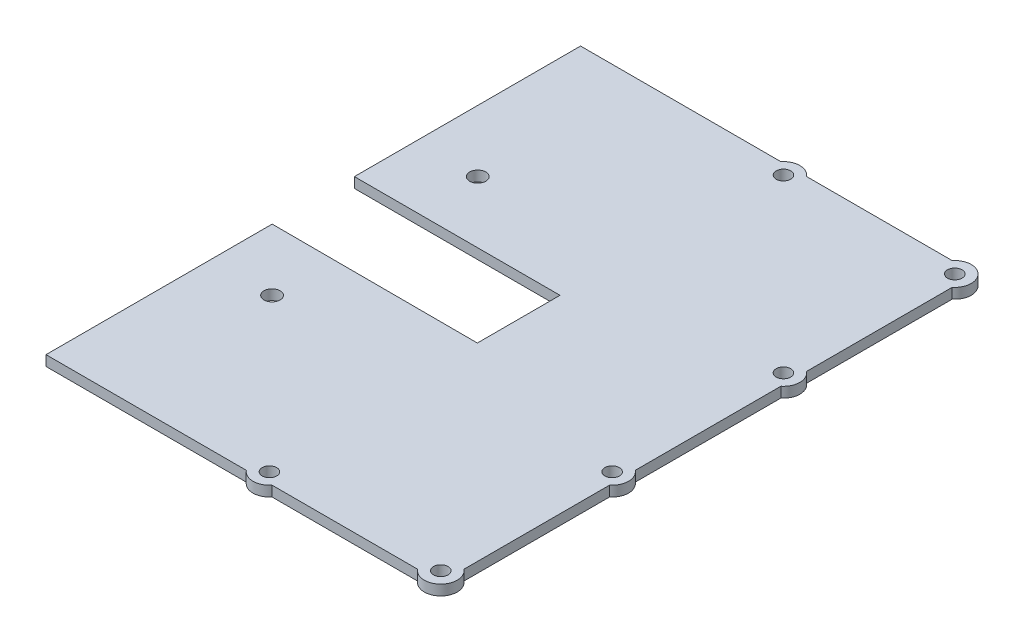
SolidWorks part; units mm, degrees
material "Aluminum"
ref_plane "Front Plane" through (0, 0, 0) normal (0, 0, 1) x (1, 0, 0)
ref_plane "Top Plane" through (0, 0, 0) normal (0, 1, 0) x (1, 0, 0)
ref_plane "Right Plane" through (0, 0, 0) normal (1, 0, 0) x (0, 0, -1)
sketch "Sketch1" plane through (0, 0, 0) normal (0, 1, 0) x (1, 0, 0)
  circle A0 centre (65.8401, 3.175) radius 2.2479
  circle A1 centre (118.7568, 3.175) radius 2.2479
  circle A2 centre (118.7568, 56.0917) radius 2.2479
  circle A3 centre (118.7568, 109.0083) radius 2.2479
  circle A4 centre (118.7568, 161.925) radius 2.2479
  circle A5 centre (65.8401, 161.925) radius 2.2479
  line B0 (0, 165.1) -> (61.8745, 165.1)
  line B1 (0, 95.25) -> (0, 165.1)
  line B2 (0, 69.85) -> (0, 0)
  line B3 (61.8745, 0) -> (0, 0)
  line B4 (114.7912, 0) -> (69.8057, 0)
  line B5 (121.9318, 52.1261) -> (121.9318, 7.1406)
  line B6 (121.9318, 105.0428) -> (121.9318, 60.0572)
  line B7 (121.9318, 157.9594) -> (121.9318, 112.9739)
  line B8 (69.8057, 165.1) -> (114.7912, 165.1)
  line B9 (0, 95.25) -> (63.5, 95.25)
  line B10 (63.5, 95.25) -> (63.5, 69.7245)
  line B11 (63.5, 69.7245) -> (0, 69.85)
  arc B12 (69.8057, 165.1) -> (61.8745, 165.1) centre (65.8401, 161.925) ccw
  arc B13 (61.8745, 0) -> (69.8057, 0) centre (65.8401, 3.175) ccw
  arc B14 (114.7912, 0) -> (121.9318, 7.1406) centre (118.7568, 3.175) ccw
  arc B15 (121.9318, 52.1261) -> (121.9318, 60.0572) centre (118.7568, 56.0917) ccw
  arc B16 (121.9318, 105.0428) -> (121.9318, 112.9739) centre (118.7568, 109.0083) ccw
  arc B17 (121.9318, 157.9594) -> (114.7912, 165.1) centre (118.7568, 161.925) ccw
  dimension "D1" = 4.4958
sketch_block_instance "Block-bottomplate-1"
sketch_block "Block-bottomplate" parameters "D1"=63.5
extrude "Boss-Extrude1" add sketch "Sketch1" along normal blind 3.175
sketch "Sketch2" plane through (0, 0, 0) normal (0, -1, 0) x (1, 0, 0)
  line L0 (63.5, -69.7245) -> (0, -69.85) construction
  line L1 (0, -95.25) -> (63.5, -95.25) construction
  line L2 (0, -165.1) -> (0, -95.25) construction
  circle A0 centre (19.05, -50.7623) radius 2.4892
  circle A1 centre (19.05, -114.3) radius 2.4892
  dimension "D3" = 4.9784
  dimension "D1" = 19.05
  dimension "D2" = 19.05
  dimension "D4" = 19.05
extrude "Cut-Extrude1" cut sketch "Sketch2" against normal through all
equation "\"Unit Measure\"= \"BoundingVolume\" / \"Thickness\"'in^2"
